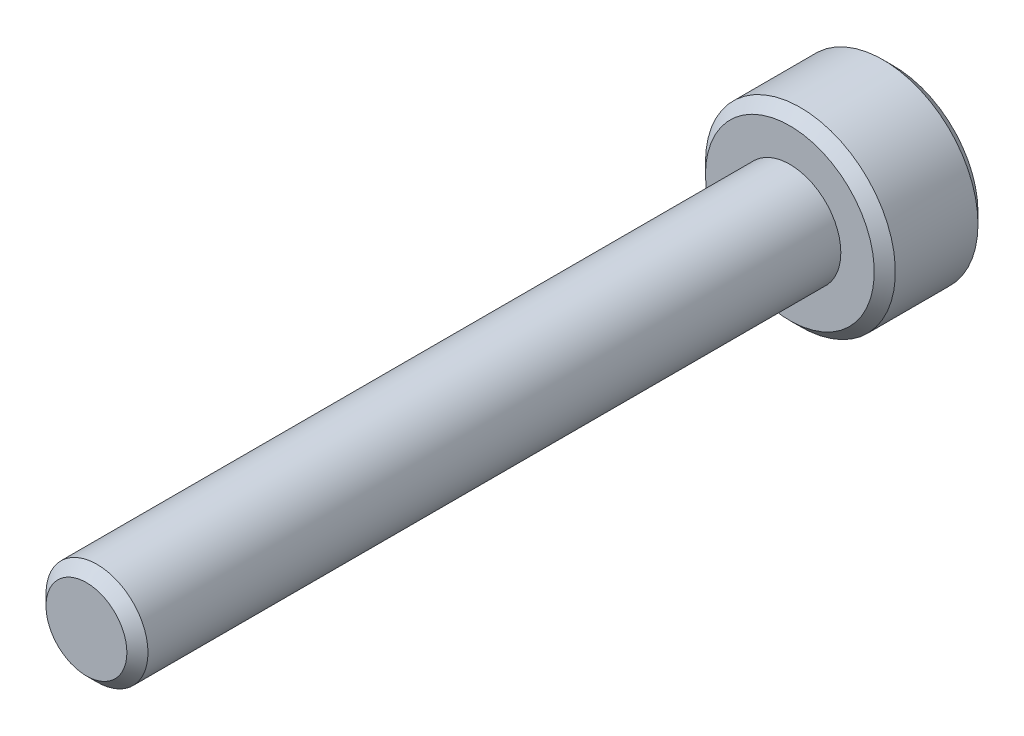
SolidWorks part; units mm, degrees
material "AISI 1020"
ref_plane "Front" through (0, 0, 0) normal (0, 0, 1) x (1, 0, 0)
ref_plane "Top" through (0, 0, 0) normal (0, 1, 0) x (1, 0, 0)
ref_plane "Right" through (0, 0, 0) normal (1, 0, 0) x (0, 0, -1)
sketch "Skizze1" plane through (0, 0, 0) normal (0, 0, 1) x (1, 0, 0)
  circle A0 centre (0, 0) radius 2.7
  dimension "D1" = 5.4
extrude "Aufsatz-Linear austragen1" add sketch "Skizze1" along normal blind 2.95
sketch "Skizze2" plane through (0, 0, 2.95) normal (0, 0, 1) x (1, 0, 0)
  circle A0 centre (0, 0) radius 1.45
  dimension "D1" = 2.9
extrude "Aufsatz-Linear austragen2" add sketch "Skizze2" along normal blind 20
chamfer "Fase1" distance 0.3 angle 45 3 edges at (2.7, 0, 2.95) (2.7, 0, 0) (1.45, 0, 22.95)
sketch "Skizze3" plane through (0, 0, 0) normal (0, 0, -1) x (-1, 0, 0)
  line L0 (1.25, 0) -> (0, 0) construction
  line L1 (1.25, 0.7217) -> (0, 1.4434)
  line L2 (0, 1.4434) -> (-1.25, 0.7217)
  line L3 (-1.25, 0.7217) -> (-1.25, -0.7217)
  line L4 (-1.25, -0.7217) -> (0, -1.4434)
  line L5 (0, -1.4434) -> (1.25, -0.7217)
  line L6 (1.25, -0.7217) -> (1.25, 0.7217)
  circle A0 centre (0, 0) radius 1.25 construction
  dimension "D1" = 2.5
extrude "Schnitt-Linear austragen1" cut sketch "Skizze3" against normal blind 2.5
